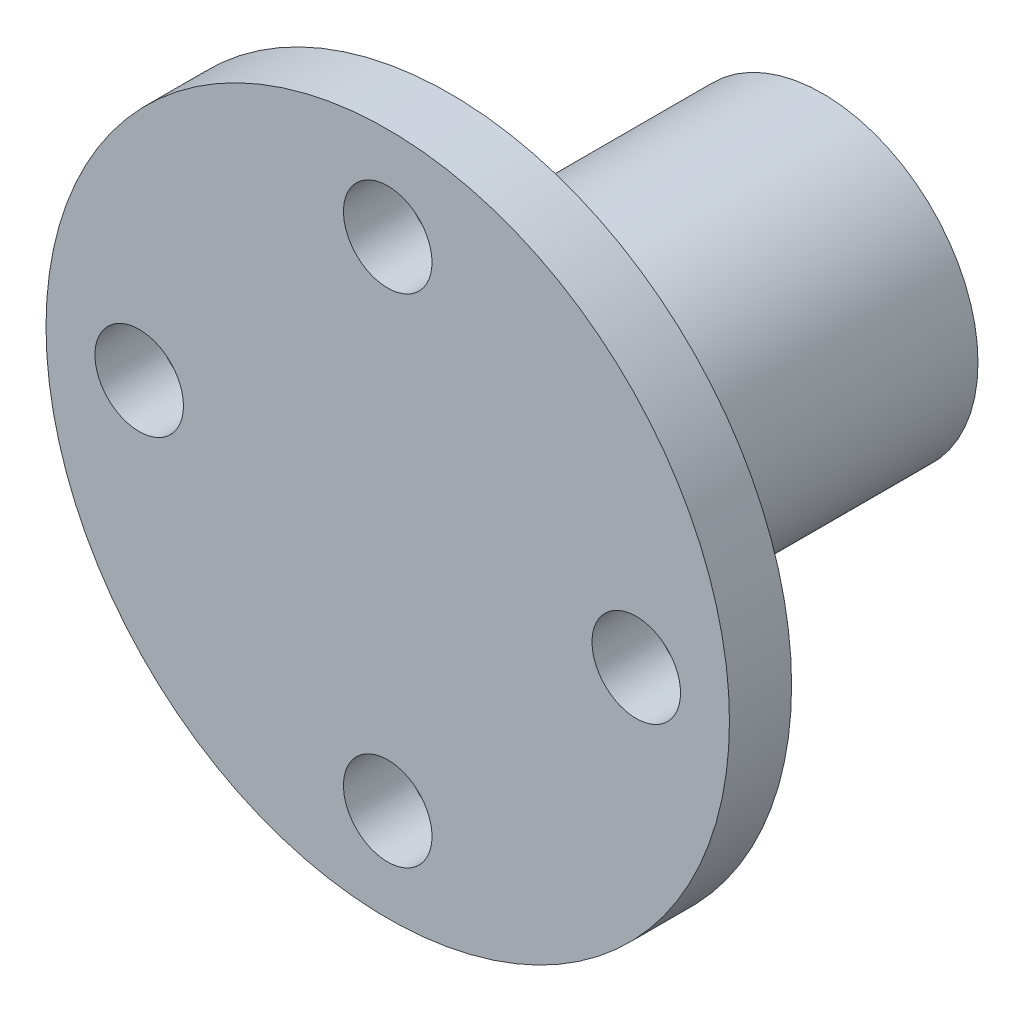
SolidWorks part; units mm, degrees
ref_plane "Front Plane" through (0, 0, 0) normal (0, 0, 1) x (1, 0, 0)
ref_plane "Top Plane" through (0, 0, 0) normal (0, 1, 0) x (1, 0, 0)
ref_plane "Right Plane" through (0, 0, 0) normal (1, 0, 0) x (0, 0, -1)
sketch "Sketch1" plane through (0, 0, 0) normal (0, 0, 1) x (1, 0, 0)
  line L0 (0, 11) -> (0, 5) construction
  circle A0 centre (0, 0) radius 11
  circle A1 centre (0, 0) radius 5
  circle A2 centre (0, 0) radius 3
  circle A3 centre (0, 8) radius 1.425
  circle A4 centre (8, 0) radius 1.425
  circle A5 centre (0, -8) radius 1.425
  circle A6 centre (-8, 0) radius 1.425
  point P7 (0, 8)
  point P19 (0, 0)
  dimension "D1" = 22
  dimension "D2" = 10
  dimension "D3" = 6
  dimension "D4" = 2.85
  dimension "D5" = 4
extrude "Boss-Extrude1" add sketch "Sketch1" along normal blind 2 contours A0 A3 A1 A6 A5 A4 | A1 region at (-10.6889, 0, 0)
extrude "Boss-Extrude2" add sketch "Sketch1<4>" against normal blind 12 contours A1 A2 region at (-4.8586, 0, 0)
sketch "Sketch1<4>" plane through (0, 0, 0) normal (0, 0, 1) x (1, 0, 0) same geometry as "Sketch1"
